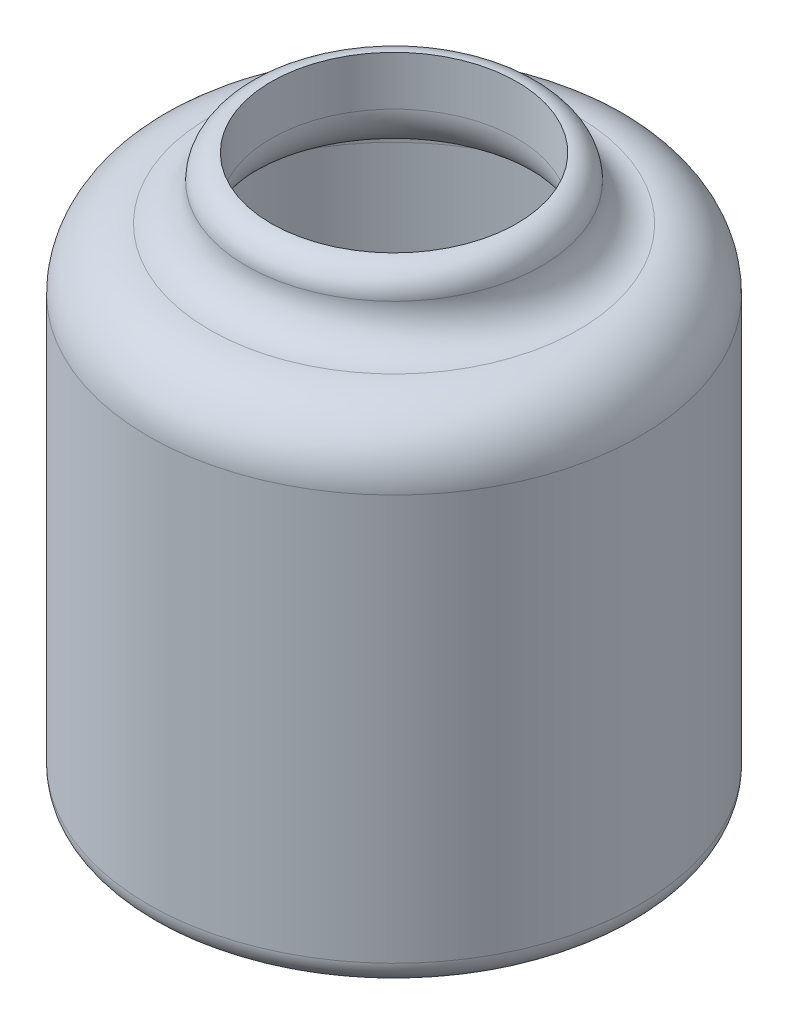
SolidWorks part; units mm, degrees
ref_plane "Front Plane" through (0, 0, 0) normal (0, 0, 1) x (1, 0, 0)
ref_plane "Top Plane" through (0, 0, 0) normal (0, 1, 0) x (1, 0, 0)
ref_plane "Right Plane" through (0, 0, 0) normal (1, 0, 0) x (0, 0, -1)
sketch "Sketch1" plane through (0, 0, 0) normal (0, 1, 0) x (1, 0, 0)
  circle A0 centre (0, 0) radius 100
  dimension "D1" = 200
extrude "Boss-Extrude2" add sketch "Sketch1" along normal blind 200
ref_plane "Plane1" through (0, 200, 0) normal (0, 1, 0) x (1, 0, 0)
sketch "Sketch4" plane through (0, 200, 0) normal (0, 1, 0) x (1, 0, 0)
  circle A0 centre (0, 0) radius 60
  dimension "D1" = 120
extrude "Boss-Extrude5" add sketch "Sketch4" along normal blind 25
ref_plane "Plane2" through (0, 225, 0) normal (0, 1, 0) x (1, 0, 0)
sketch "Sketch5" plane through (0, 225, 0) normal (0, 1, 0) x (1, 0, 0)
  circle A0 centre (0, 0) radius 60
  circle A1 centre (0, 0) radius 50
  dimension "D1" = 100
extrude "Cut-Extrude2" cut sketch "Sketch5" against normal blind 210 contours A1
fillet "Fillet2" radius 10 1 edges at (0, 0, 100)
fillet "Fillet3" radius 10 1 edges at (0, 225, 60)
fillet "Fillet4" radius 15 1 edges at (0, 200, 60)
fillet "Fillet5" radius 25 1 edges at (0, 200, 100)
ref_plane "Plane3" through (0, 15, 0) normal (0, 1, 0) x (1, 0, 0)
sketch "Sketch6" plane through (0, 15, 0) normal (0, 1, 0) x (1, 0, 0)
  circle A0 centre (0, 0) radius 90
  dimension "D1" = 180
extrude "Cut-Extrude4" cut sketch "Sketch6" along normal blind 170
fillet "Fillet7" radius 20 1 edges at (0, 185, 90)
fillet "Fillet8" radius 20 1 edges at (0, 185, 50)
fillet "Fillet9" radius 10 1 edges at (0, 15, 90)
